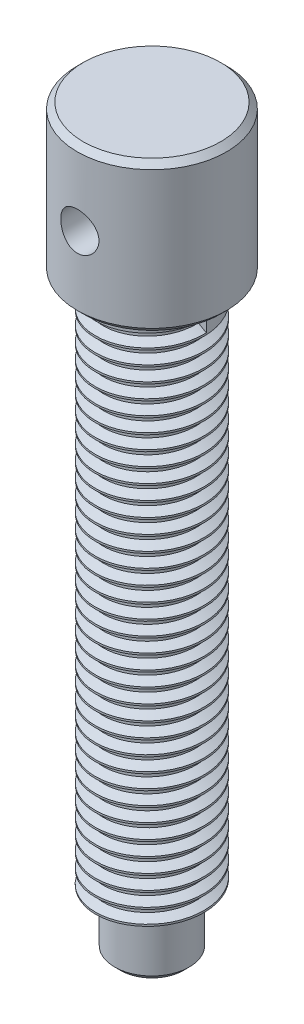
SolidWorks part; units mm, degrees
ref_plane "Front Plane" through (0, 0, 0) normal (0, 0, 1) x (1, 0, 0)
ref_plane "Top Plane" through (0, 0, 0) normal (0, 1, 0) x (1, 0, 0)
ref_plane "Right Plane" through (0, 0, 0) normal (1, 0, 0) x (0, 0, -1)
sketch "Sketch1" plane through (0, 0, 0) normal (0, 1, 0) x (1, 0, 0)
  circle A0 centre (0, 0) radius 6.35
  dimension "D1" = 12.7
extrude "Boss-Extrude1" add sketch "Sketch1" against normal blind 12.7
sketch "Sketch2" plane through (0, -12.7, 0) normal (0, -1, 0) x (1, 0, 0)
  circle A0 centre (0, 0) radius 4.625
  dimension "D1" = 9.25
extrude "Boss-Extrude2" add sketch "Sketch2" along normal blind 45
sketch "Sketch3" plane through (0, -57.7, 0) normal (0, -1, 0) x (1, 0, 0)
  circle A0 centre (0, 0) radius 3.175
  dimension "D1" = 6.35
extrude "Boss-Extrude3" add sketch "Sketch3" along normal blind 5
chamfer "Chamfer1" distance 0.5 angle 45 3 edges at (0, -62.7, -3.175) (0, 0, 6.35) (0, -12.7, 6.35)
thread "Thread1" pitch 1.25 method cut profile "Thread Profile1" start angle 0, offset 2, length 45, pitch 1.25, diameter 9.25
ref_plane "Plane1" through (4.625, -59.7, 0) normal (0, 0, 1) x (1, 0, 0)
sketch "Thread Profile1" plane through (4.625, -59.7, 0) normal (0, 0, 1) x (1, 0, 0)
  line L0 (0, 0) -> (0, 1.25) construction
  line L11 (0, 0) -> (0, 1.0937)
  line L12 (0, 1.0937) -> (-0.6766, 0.7031)
  line L13 (-0.6766, 0.7031) -> (-0.6766, 0.3906)
  line L15 (-0.6766, 0.3906) -> (0, 0)
  line L17 (-0.6766, 0.5469) -> (0, 0.5469) construction
  point P2 (0, 0)
  dimension "Pitch" = 1.25
  dimension "Profile_Angle" = 60
  dimension "Profile_Land" = 0.3125
  dimension "Profile_Height" = 0.6766
sketch "Sketch8" plane through (0, 0, 0) normal (0, 0, 1) x (1, 0, 0)
  line L0 (5.85, 0) -> (-5.85, 0) construction
  circle A0 centre (0, -6.35) radius 1.625
  point P5 (0, 0)
  point P6 (0, 0)
  dimension "D1" = 3.25
  dimension "D2" = 6.35
extrude "Cut-Extrude1" cut sketch "Sketch8" against normal mid plane 40
